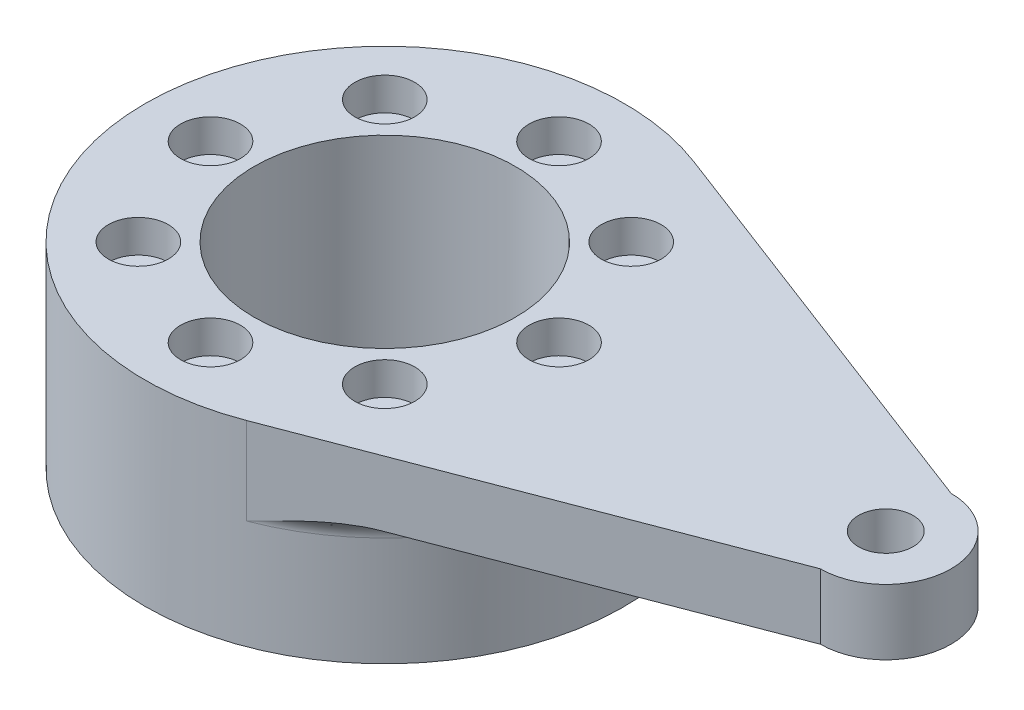
SolidWorks part; units mm, degrees
material "6061 合金"
ref_plane "前视基准面" through (0, 0, 0) normal (0, 0, 1) x (1, 0, 0)
ref_plane "上视基准面" through (0, 0, 0) normal (0, 1, 0) x (1, 0, 0)
ref_plane "右视基准面" through (0, 0, 0) normal (1, 0, 0) x (0, 0, -1)
sketch "草图1" plane through (0, 0, 0) normal (0, 1, 0) x (1, 0, 0)
  circle A0 centre (0, 0) radius 22
  circle A1 centre (0, 0) radius 16 construction
  circle A2 centre (-16, 0) radius 1.25
  circle A4 centre (-11.3137, 11.3137) radius 1.25
  circle A6 centre (0, 16) radius 1.25
  circle A8 centre (11.3137, 11.3137) radius 1.25
  circle A10 centre (16, 0) radius 1.25
  circle A12 centre (11.3137, -11.3137) radius 1.25
  circle A14 centre (0, -16) radius 1.25
  circle A16 centre (-11.3137, -11.3137) radius 1.25
  circle A18 centre (-14.7821, 6.1229) radius 1.25 [skipped]
  circle A19 centre (-6.1229, 14.7821) radius 1.25 [skipped]
  circle A20 centre (6.1229, 14.7821) radius 1.25 [skipped]
  circle A21 centre (14.7821, 6.1229) radius 1.25 [skipped]
  circle A22 centre (14.7821, -6.1229) radius 1.25 [skipped]
  circle A23 centre (6.1229, -14.7821) radius 1.25 [skipped]
  circle A24 centre (-6.1229, -14.7821) radius 1.25 [skipped]
  circle A25 centre (-14.7821, -6.1229) radius 1.25 [skipped]
  point P39 (0, 0)
  dimension "D1" = 16
extrude "凸台-拉伸1" add sketch "草图1" along normal blind 12
sketch "草图3" plane through (0, 12, 0) normal (0, 1, 0) x (1, 0, 0)
  line L0 (0, 0) -> (35.7311, 0) construction
  line L1 (46, -6) -> (7.8406, -20.5554)
  line L2 (46, 6) -> (7.8406, 20.5554)
  circle A0 centre (0, 0) radius 22
  circle A1 centre (0, 0) radius 22
  circle A2 centre (0, 0) radius 22
  circle A3 centre (46, 0) radius 6
  circle A4 centre (46, 0) radius 2.5
  circle M3 centre (0, -16) radius 1.25
  circle M4 centre (16, 0) radius 1.25
  circle M5 centre (0, 16) radius 1.25
  circle M6 centre (-16, 0) radius 1.25
  circle M7 centre (0, 0) radius 22
  circle M8 centre (-11.3137, 11.3137) radius 1.25
  circle M9 centre (11.3137, 11.3137) radius 1.25
  circle M10 centre (11.3137, -11.3137) radius 1.25
  circle M11 centre (-11.3137, -11.3137) radius 1.25
  dimension "D1" = 0
extrude "凸台-拉伸2" add sketch "草图3" along normal blind 6 contours A2 L0 A3 L2 | L0 A2 M7 M6 M4 M5 M9 M8 | L0 A2 M7 M4 M6 M10 M11 M3 | L0 L1 A3 M7 | A3 L0 A4 | L0 A3 A4 region at (17.6051, 12, 12.1271) region at (18.5795, 12, -12.7983) region at (50.1226, 12, -4.1226)
sketch "草图2" plane through (0, 0, 0) normal (0, -1, 0) x (1, 0, 0)
  circle A0 centre (-16, 0) radius 1.25 construction
  circle A1 centre (0, 0) radius 22
  circle A2 centre (0, 0) radius 22
  circle A4 centre (0, 0) radius 16 construction
  circle A6 centre (-14.7821, 6.1229) radius 2.05
  circle A10 centre (6.1229, 14.7821) radius 2.05
  circle A14 centre (14.7821, -6.1229) radius 2.05
  circle A18 centre (-6.1229, -14.7821) radius 2.05
  point P40 (0, 0)
  dimension "D1" = 0
extrude "切除-拉伸1" cut sketch "草图2" against normal blind 3.5 contours A18 | A6 | A14 | A10 region at (-14.7821, 0, 6.1229) region at (6.1229, 0, 14.7821) region at (14.7821, 0, -6.1229) region at (-6.1229, 0, -14.7821)
sketch "草图4" plane through (0, 18, 0) normal (0, 1, 0) x (1, 0, 0)
  line L2 (7.8406, -20.5554) -> (46, -6)
  line L3 (46, 6) -> (7.8406, 20.5554)
  line L4 (7.8406, -20.5554) -> (46, -6)
  line L5 (46, 6) -> (7.8406, 20.5554)
  circle A0 centre (0, 0) radius 16 construction
  circle A1 centre (-16, 0) radius 2.75
  arc A2 (46, -6) -> (46, 6) centre (46, 0) ccw
  arc A3 (7.8406, 20.5554) -> (7.8406, -20.5554) centre (0, 0) ccw
  arc A4 (46, -6) -> (46, 6) centre (46, 0) ccw
  arc A5 (7.8406, 20.5554) -> (7.8406, -20.5554) centre (0, 0) ccw
  circle A6 centre (-11.3137, 11.3137) radius 2.75
  circle A7 centre (0, 16) radius 2.75
  circle A8 centre (11.3137, 11.3137) radius 2.75
  circle A9 centre (16, 0) radius 2.75
  circle A10 centre (11.3137, -11.3137) radius 2.75
  circle A11 centre (0, -16) radius 2.75
  circle A12 centre (-11.3137, -11.3137) radius 2.75
  point P26 (0, 0)
  circle M5 centre (-16, 0) radius 1.25
  circle M6 centre (16, 0) radius 1.25
  circle M12 centre (0, 16) radius 1.25
  circle M13 centre (11.3137, 11.3137) radius 1.25
  circle M14 centre (-11.3137, 11.3137) radius 1.25
  circle M15 centre (11.3137, -11.3137) radius 1.25
  circle M16 centre (-11.3137, -11.3137) radius 1.25
  circle M17 centre (0, -16) radius 1.25
  dimension "D1" = 0
extrude "切除-拉伸2" cut sketch "草图4" against normal blind 3 contours A1 M5 | A12 M16 | A6 M14 | A7 M12 | A8 M13 | A9 M6 | A10 M15 | A11 M17 region at (-18.6722, 18, 0) region at (-13.9859, 18, -11.3137) region at (-2.6722, 18, -16) region at (8.6415, 18, -11.3137) region at (13.3278, 18, 0) region at (8.6415, 18, 11.3137) region at (-2.6722, 18, 16) region at (-13.9859, 18, 11.3137)
sketch "草图5" plane through (0, 18, 0) normal (0, 1, 0) x (1, 0, 0)
  line L2 (7.8406, -20.5554) -> (46, -6)
  line L3 (46, 6) -> (7.8406, 20.5554)
  line L4 (7.8406, -20.5554) -> (46, -6)
  line L5 (46, 6) -> (7.8406, 20.5554)
  circle A0 centre (0, 0) radius 12
  arc A2 (46, -6) -> (46, 6) centre (46, 0) ccw
  arc A3 (7.8406, 20.5554) -> (7.8406, -20.5554) centre (0, 0) ccw
  arc A4 (46, -6) -> (46, 6) centre (46, 0) ccw
  arc A5 (7.8406, 20.5554) -> (7.8406, -20.5554) centre (0, 0) ccw
  dimension "D1" = 0
extrude "切除-拉伸3" cut sketch "草图5" against normal through all contours A0 region at (0, 18, 0)
fillet "圆角1" radius 2 1 edges at (22, 12, 0)
